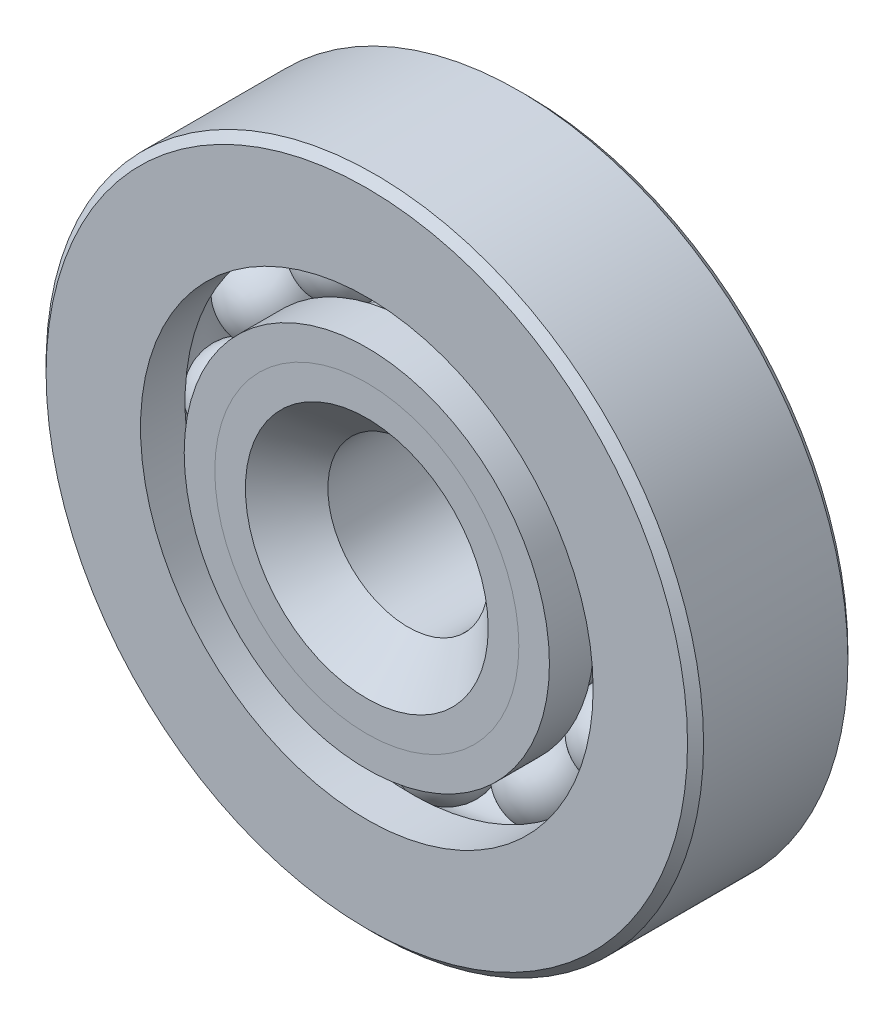
SolidWorks part; units mm, degrees
ref_plane "Front Plane" through (0, 0, 0) normal (0, 0, 1) x (1, 0, 0)
ref_plane "Top Plane" through (0, 0, 0) normal (0, 1, 0) x (1, 0, 0)
ref_plane "Right Plane" through (0, 0, 0) normal (1, 0, 0) x (0, 0, -1)
sketch "Sketch1" plane through (0, 0, 0) normal (1, 0, 0) x (0, 0, -1)
  line L0 (-3.9688, 0) -> (3.9688, 0) construction
  line L1 (0, 16.2719) -> (0, -16.2719) construction
  line L2 (3.5719, 16.2719) -> (-3.5719, 16.2719)
  line L3 (-3.5719, 16.2719) -> (-3.9688, 15.875)
  line L4 (-3.9688, 15.875) -> (-3.9688, 11.2019)
  line L5 (-3.9688, 11.2019) -> (-1.7639, 11.2019)
  line L6 (3.9688, 11.2019) -> (1.7639, 11.2019)
  line L7 (3.9688, 15.875) -> (3.9688, 11.2019)
  line L8 (3.5719, 16.2719) -> (3.9688, 15.875)
  line L9 (0, 16.2719) -> (0, 10.1203) construction
  line L10 (0, 10.1203) -> (0, 3.9688) construction
  arc A0 (-1.7639, 11.2019) -> (1.7639, 11.2019) centre (0, 10.1203) cw
  point P14 (0, 3.9688)
  dimension "D3" = 3.5278
  dimension "D1" = 45
  dimension "Width" = 7.9375
  dimension "OD" = 32.5437
  dimension "D2" = 0.3969
  dimension "Shaft Dia" = 7.9375
  dimension "D4" = 1.0816
revolve "Revolve1" add sketch "Sketch1" angle 360 about L0
sketch "Sketch2" plane through (0, 0, 0) normal (1, 0, 0) x (0, 0, -1)
  line L0 (-3.9688, 9.0387) -> (-1.7639, 9.0387)
  line L1 (-3.9688, 15.875) -> (-3.9688, -15.875) construction
  line L2 (-3.9688, 9.0387) -> (-3.9688, 7.5244)
  line L3 (-3.9688, 7.5244) -> (-2.4544, 6.01)
  line L4 (-2.4544, 6.01) -> (0, 6.01)
  line L5 (0, 16.2719) -> (0, -16.2719) construction
  line L6 (0, 6.01) -> (0, 8.0512)
  line L7 (0, 8.0512) -> (0, 3.9688) construction
  line L8 (-3.9688, 9.0387) -> (-3.9688, 6.01) construction
  line L9 (-3.9688, 6.01) -> (-2.4544, 6.01) construction
  arc A0 (-1.7639, 9.0387) -> (0, 8.0512) centre (0, 10.1203) ccw
  arc A1 (1.7639, 11.2019) -> (-1.7639, 11.2019) centre (0, 10.1203) ccw construction
  circle A2 centre (0, 10.1203) radius 2.0691 construction
  dimension "D1" = 45
revolve "Revolve2" add sketch "Sketch2" angle 360 about L0
sketch "Sketch3" plane through (0, 0, 0) normal (1, 0, 0) x (0, 0, -1)
  line L0 (-3.9688, 7.5244) -> (-2.4544, 6.01)
  line L1 (-2.4544, 6.01) -> (0, 6.01)
  line L2 (0, 6.01) -> (0, 8.0512)
  line L3 (-3.9688, 7.5244) -> (-3.9688, 6.01)
  line L4 (-3.9688, 9.0387) -> (-3.9688, 6.01) construction
  line L5 (-3.9688, 6.01) -> (-1.9275, 3.9688)
  line L6 (-1.9275, 3.9688) -> (3.5719, 3.9688)
  line L7 (3.5719, 16.2719) -> (3.5719, -16.2719) construction
  line L8 (3.5719, 3.9688) -> (3.9688, 4.3656)
  line L9 (3.9688, -15.875) -> (3.9688, 15.875) construction
  line L10 (3.9688, 4.3656) -> (3.9688, 9.0387)
  line L11 (3.9688, 9.0387) -> (1.7639, 9.0387)
  line L13 (3.5719, 16.2719) -> (3.9688, 15.875) construction
  circle A0 centre (0, 10.1203) radius 2.0691 construction
  arc A1 (1.7639, 9.0387) -> (0, 8.0512) centre (0, 10.1203) cw
revolve "Revolve3" add sketch "Sketch3" angle 360 about L0
sketch "Sketch4" plane through (0, 0, 0) normal (1, 0, 0) x (0, 0, -1)
  line L0 (-2.0691, 10.1203) -> (2.0691, 10.1203)
  circle A1 centre (0, 10.1203) radius 2.0691 construction
  arc A2 (-2.0691, 10.1203) -> (2.0691, 10.1203) centre (0, 10.1203) cw
  arc A3 (1.7639, 11.2019) -> (-1.7639, 11.2019) centre (0, 10.1203) ccw construction
revolve "Revolve4" add sketch "Sketch4" angle 360 about L0
ref_axis "Axis1" through (0, 0, -3.9688) along (0, 0, 1)
pattern_circular "CirPattern1" count 12 every 30 about axis through (0, 0, -3.9688) along (0, 0, 1) of bodies 104
equation "\"D2@Sketch1\" = \"Width@Sketch1\"*.05"
equation "\"D3@Sketch1\" = \"Width@Sketch1\"/2.25"
equation "\"D4@Sketch1\" = (((\"OD@Sketch1\"-\"Width@Sketch1\")/2)/3.25)/3.5"
equation "\"D2@CirPattern1\" = 360/\"Balls@CirPattern1\""
